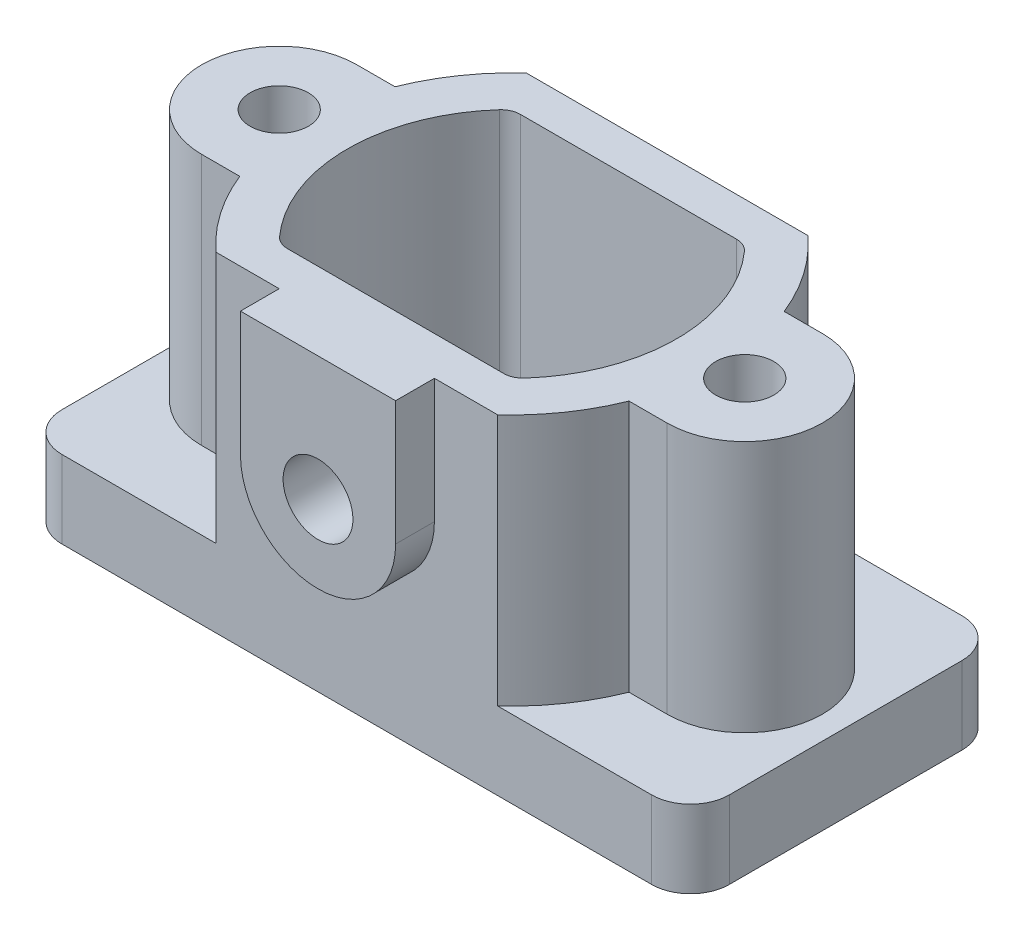
SolidWorks part; units mm, degrees
ref_plane "前视基准面" through (0, 0, 0) normal (0, 0, 1) x (1, 0, 0)
ref_plane "上视基准面" through (0, 0, 0) normal (0, 1, 0) x (1, 0, 0)
ref_plane "右视基准面" through (0, 0, 0) normal (1, 0, 0) x (0, 0, -1)
sketch "草图1" plane through (0, 0, 0) normal (0, 1, 0) x (1, 0, 0)
  line L1 (-86, -40) -> (86, -40)
  line L2 (-86, -40) -> (-86, 40)
  line L3 (-86, 40) -> (86, 40)
  line L4 (86, -40) -> (86, 40)
  line L7 (-30, -12.5) -> (-18.7083, -12.5)
  line L8 (-30, -12.5) -> (-30, 12.5)
  line L9 (-30, 12.5) -> (-18.7083, 12.5)
  line L10 (30, -12.5) -> (30, 12.5)
  line L14 (18.7083, 12.5) -> (30, 12.5)
  line L17 (18.7083, -12.5) -> (30, -12.5)
  arc A0 (-18.7083, -12.5) -> (18.7083, -12.5) centre (0, 0) ccw
  arc A1 (18.7083, 12.5) -> (-18.7083, 12.5) centre (0, 0) ccw
  point P0 (0, 0)
extrude "凸台-拉伸1" add sketch "草图1" along normal blind 20
fillet "圆角1" radius 10 4 edges at (86, 10, -40) (86, 10, 40) (-86, 10, 40) (-86, 10, -40)
ref_plane "基准面1" through (0, 20, 0) normal (0, 1, 0) x (1, 0, 0)
sketch "草图2" plane through (0, 20, 0) normal (0, 1, 0) x (1, 0, 0)
  line L0 (-36.2767, 40) -> (36.2767, 40)
  line L1 (76, 40) -> (-76, 40) construction
  line L2 (-36.2767, -40) -> (36.2767, -40)
  line L3 (-76, -40) -> (76, -40) construction
  line L4 (-60, 20) -> (-50.1597, 20)
  line L5 (-60, -20) -> (-50.1597, -20)
  line L6 (50.1597, -20) -> (60, -20)
  line L7 (50.1597, 20) -> (60, 20)
  arc A0 (-36.2767, 40) -> (-50.1597, 20) centre (0, 0) ccw
  circle A1 centre (-60, 0) radius 7.5
  circle A2 centre (60, 0) radius 7.5
  arc A3 (-60, 20) -> (-60, -20) centre (-60, 0) ccw
  arc A4 (60, -20) -> (60, 20) centre (60, 0) ccw
  arc A5 (36.2767, -40) -> (50.1597, -20) centre (0, 0) ccw
  arc A6 (-50.1597, -20) -> (-36.2767, -40) centre (0, 0) ccw
  arc A8 (50.1597, 20) -> (36.2767, 40) centre (0, 0) ccw
extrude "凸台-拉伸2" add sketch "草图2" along normal blind 65
sketch "草图3" plane through (0, 20, 0) normal (0, 1, 0) x (1, 0, 0)
  line L1 (-30, 30) -> (30, 30)
  line L3 (-30, -30) -> (30, -30)
  arc A0 (-30, 30) -> (-30, -30) centre (0, 0) ccw
  arc A1 (30, -30) -> (30, 30) centre (0, 0) ccw
  point P0 (0, 0)
extrude "切除-拉伸1" cut sketch "草图3" along normal blind 65
ref_plane "基准面2" through (0, 0, 40) normal (0, 0, 1) x (1, 0, 0)
sketch "草图4" plane through (0, 0, 40) normal (0, 0, 1) x (1, 0, 0)
  line L0 (-20, 53) -> (-20, 85)
  line L1 (-36.2767, 85) -> (36.2767, 85) construction
  line L2 (-20, 85) -> (20, 85)
  line L3 (20, 85) -> (20, 53)
  arc A0 (-20, 53) -> (20, 53) centre (0, 53) ccw
extrude "凸台-拉伸3" add sketch "草图4" along normal blind 10
sketch "草图5" plane through (0, 0, 40) normal (0, 0, 1) x (1, 0, 0)
  circle A0 centre (0, 53) radius 9
extrude "切除-拉伸2" cut sketch "草图5" against normal blind 10 and the other way blind 10
fillet "圆角2" radius 5 4 edges at (-30, 52.5, 30) (30, 52.5, 30) (30, 52.5, -30) (-30, 52.5, -30)
